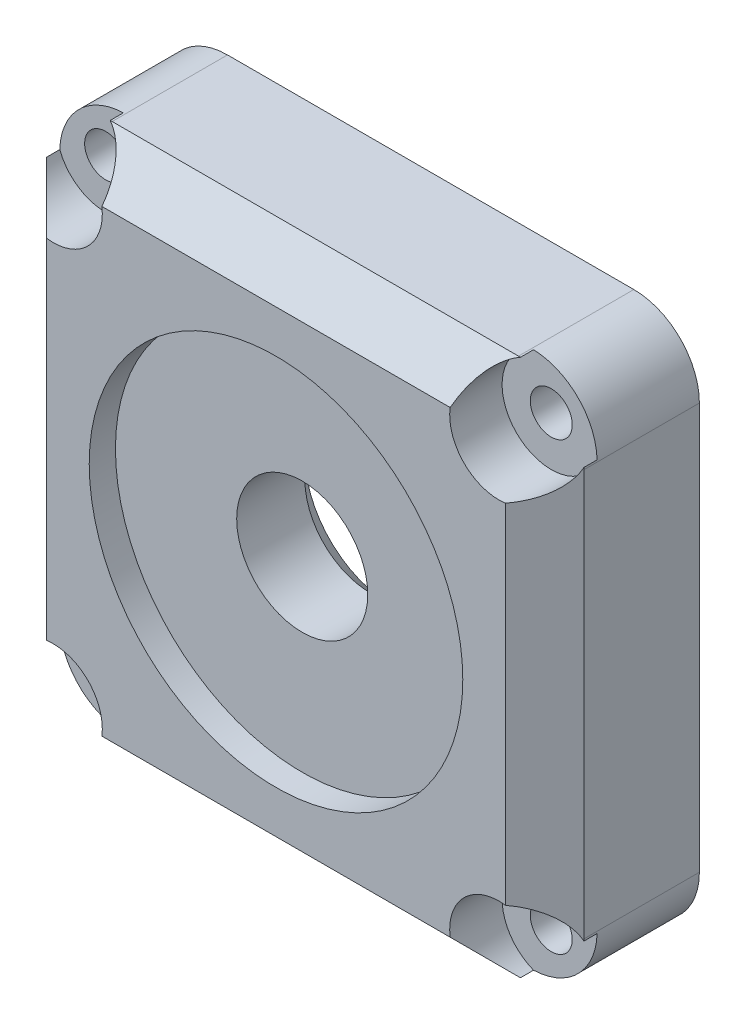
SolidWorks part; units mm, degrees
ref_plane "Front" through (0, 0, 0) normal (0, 0, 1) x (1, 0, 0)
ref_plane "Top" through (0, 0, 0) normal (0, 1, 0) x (1, 0, 0)
ref_plane "Right" through (0, 0, 0) normal (1, 0, 0) x (0, 0, -1)
sketch "ｽｹｯﾁ1" plane through (0, 0, 0) normal (0, 0, 1) x (1, 0, 0)
  line L1 (-20.5, -20.5) -> (20.5, -20.5)
  line L2 (-20.5, -20.5) -> (-20.5, 20.5)
  line L3 (-20.5, 20.5) -> (20.5, 20.5)
  line L4 (20.5, -20.5) -> (20.5, 20.5)
  line L5 (-20.5, -20.5) -> (20.5, 20.5) construction
  line L6 (-20.5, 20.5) -> (20.5, -20.5) construction
  point P0 (0, 0)
  dimension "D1" = 41
extrude "ﾎﾞｽ - 押し出し1" add sketch "ｽｹｯﾁ1" along normal blind 11.8
chamfer "面取り1" distance 3 angle 45 4 edges at (0, -20.5, 11.8) (-20.5, 0, 11.8) (0, 20.5, 11.8) (20.5, 0, 11.8)
fillet "ﾌｨﾚｯﾄ1" radius 5 8 edges at (-19, -19, 10.3) (-20.5, -20.5, 4.4) (19, -19, 10.3) (20.5, -20.5, 4.4) (19, 19, 10.3) (20.5, 20.5, 4.4) (-19, 19, 10.3) (-20.5, 20.5, 4.4)
sketch "ｽｹｯﾁ3" plane through (0, 0, 0) normal (0, 0, -1) x (-1, 0, 0)
  circle A0 centre (0, 0) radius 16.5
  dimension "D1" = 33
extrude "ｶｯﾄ - 押し出し2" cut sketch "ｽｹｯﾁ3" against normal blind 3
sketch "ｽｹｯﾁ4" plane through (0, 0, 3) normal (0, 0, -1) x (-1, 0, 0)
  circle A0 centre (0, 0) radius 5
  dimension "D1" = 10
extrude "ｶｯﾄ - 押し出し3" cut sketch "ｽｹｯﾁ4" against normal through all
sketch "ｽｹｯﾁ5" plane through (0, 0, 0) normal (0, 0, -1) x (-1, 0, 0)
  line L0 (15.5, -20.5) -> (-15.5, -20.5) construction
  line L1 (15, 12.2) -> (-15, 12.2)
  line L2 (15, 12.2) -> (15, 18.2)
  line L3 (15, 18.2) -> (-15, 18.2)
  line L4 (-15, 12.2) -> (-15, 18.2)
  line L5 (-15, -18.2) -> (15, -18.2)
  line L6 (-15, -18.2) -> (-15, -12.2)
  line L7 (-15, -12.2) -> (15, -12.2)
  line L8 (15, -18.2) -> (15, -12.2)
  line L9 (-15.5, 20.5) -> (15.5, 20.5) construction
  point P8 (0, -18.2)
  dimension "D1" = 2.3
  dimension "D2" = 30
  dimension "D3" = 6
  dimension "D4" = 2.3
extrude "ｶｯﾄ - 押し出し4" cut sketch "ｽｹｯﾁ5" against normal up to surface (3 mm away) up to face at (-5, 0, 3)
chamfer "面取り2" distance 1.6 angle 45 1 edges at (-5, 0, 3)
sketch "ｽｹｯﾁ6" plane through (0, 0, 11.8) normal (0, 0, 1) x (1, 0, 0)
  circle A0 centre (0, 0) radius 14.25
  dimension "D1" = 28.5
extrude "ｶｯﾄ - 押し出し5" cut sketch "ｽｹｯﾁ6" against normal blind 2
sketch "ｽｹｯﾁ7" plane through (0, -14.65, 14.65) normal (0, -0.7071, 0.7071) x (1, 0, 0)
  line L0 (15.5, -8.2731) -> (-15.5, -8.2731) construction
  line L1 (0, -7.7731) -> (1.8123, -4.6342)
  line L2 (1.8123, -4.6342) -> (-1.8123, -4.6342)
  line L3 (-1.8123, -4.6342) -> (0, -7.7731)
  line L6 (-13.9645, -4.0305) -> (13.9645, -4.0305) construction
  circle A0 centre (0, -5.6805) radius 1.0463 construction
  dimension "D1" = 0.5
  dimension "D2" = 1.65
extrude "ｶｯﾄ - 押し出し6" cut sketch "ｽｹｯﾁ7" against normal blind 1
sketch "ｽｹｯﾁ8" plane through (0, 0, 11.8) normal (0, 0, 1) x (1, 0, 0)
  line L0 (-15.5, 20.5) -> (15.5, 20.5) construction
  line L1 (17, -17) -> (-17, -17) construction
  line L2 (17, -17) -> (17, 17) construction
  line L3 (17, 17) -> (-17, 17) construction
  line L4 (-17, -17) -> (-17, 17) construction
  line L5 (17, -17) -> (-17, 17) construction
  line L6 (17, 17) -> (-17, -17) construction
  circle A0 centre (-17, 17) radius 1.6
  circle A1 centre (-17, -17) radius 1.6
  circle A2 centre (17, -17) radius 1.6
  circle A3 centre (17, 17) radius 1.6
  point P0 (0, 0)
  dimension "D2" = 3.2
  dimension "D1" = 3.5
extrude "ｶｯﾄ - 押し出し7" cut sketch "ｽｹｯﾁ8" against normal through all
sketch "ｽｹｯﾁ9" plane through (0, 0, 11.8) normal (0, 0, 1) x (1, 0, 0)
  circle A0 centre (17, 17) radius 3.75
  circle A1 centre (-17, 17) radius 3.75
  circle A2 centre (-17, -17) radius 3.75
  circle A3 centre (17, -17) radius 3.75
  dimension "D1" = 7.5
extrude "ｶｯﾄ - 押し出し8" cut sketch "ｽｹｯﾁ9" against normal blind 4
